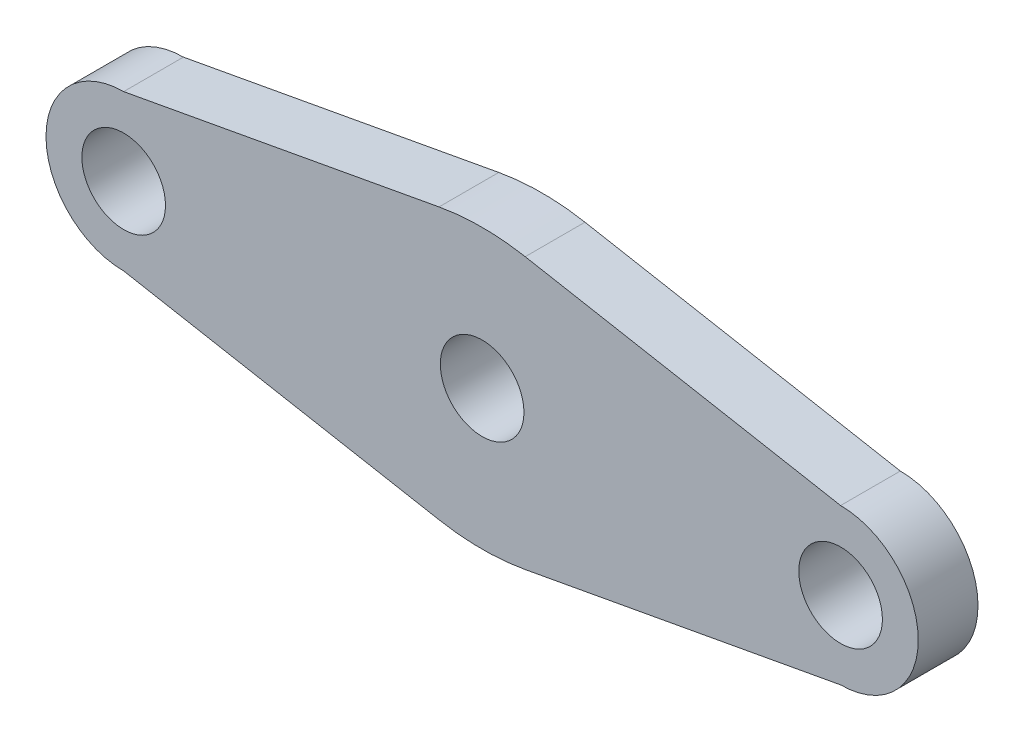
SolidWorks part; units mm, degrees
ref_plane "Front Plane" through (0, 0, 0) normal (0, 0, 1) x (1, 0, 0)
ref_plane "Top Plane" through (0, 0, 0) normal (0, 1, 0) x (1, 0, 0)
ref_plane "Right Plane" through (0, 0, 0) normal (1, 0, 0) x (0, 0, -1)
sketch "Sketch1" plane through (0, 0, 0) normal (0, 0, 1) x (1, 0, 0)
  line L0 (-15, 0) -> (15, 0)
  line L3 (0, 6) -> (0, -6) construction
  line L6 (0, 6) -> (-15, 3.25)
  line L7 (-15, -3.25) -> (0, -6)
  line L8 (0, -6) -> (15, -3.25)
  line L9 (0, 6) -> (15, 3.25)
  circle A0 centre (-15, 0) radius 1.75
  circle A1 centre (15, 0) radius 1.75
  circle A2 centre (0, 0) radius 1.75
  circle A3 centre (0, 0) radius 6
  circle A8 centre (-15, 0) radius 3.25
  circle A9 centre (15, 0) radius 3.25
  point P4 (0, 0)
  dimension "D1" = 3.5
  dimension "D3" = 12
  dimension "D4" = 1.5
  dimension "D2" = 15
extrude "Boss-Extrude1" add sketch "Sketch1" along normal blind 2.5 contours A8 A0 | A8 L0 A3 L6 | L3 L6 A3 L0 A2 | A8 L7 A3 L0 | L3 A2 L0 A3 L7 | A2 L3 L8 A3 L0 | L9 L3 A2 L0 A3 | A9 L0 A3 L8 | A9 L9 A3 L0 | A9 A1 region at (-12.7669, -2.2331, 0) region at (-8.6171, 2.5054, 0) region at (-8.6171, -2.5054, 0) region at (-2.7233, 2.6969, 0) region at (-2.7233, -2.6969, 0) region at (2.7233, 2.6969, 0) region at (2.7233, -2.6969, 0) region at (8.6171, 2.5054, 0) region at (8.6171, -2.5054, 0) region at (17.2331, 2.2331, 0)
fillet "Fillet1" radius 10 2 edges at (0, -6, 1.25) (0, 6, 1.25)
